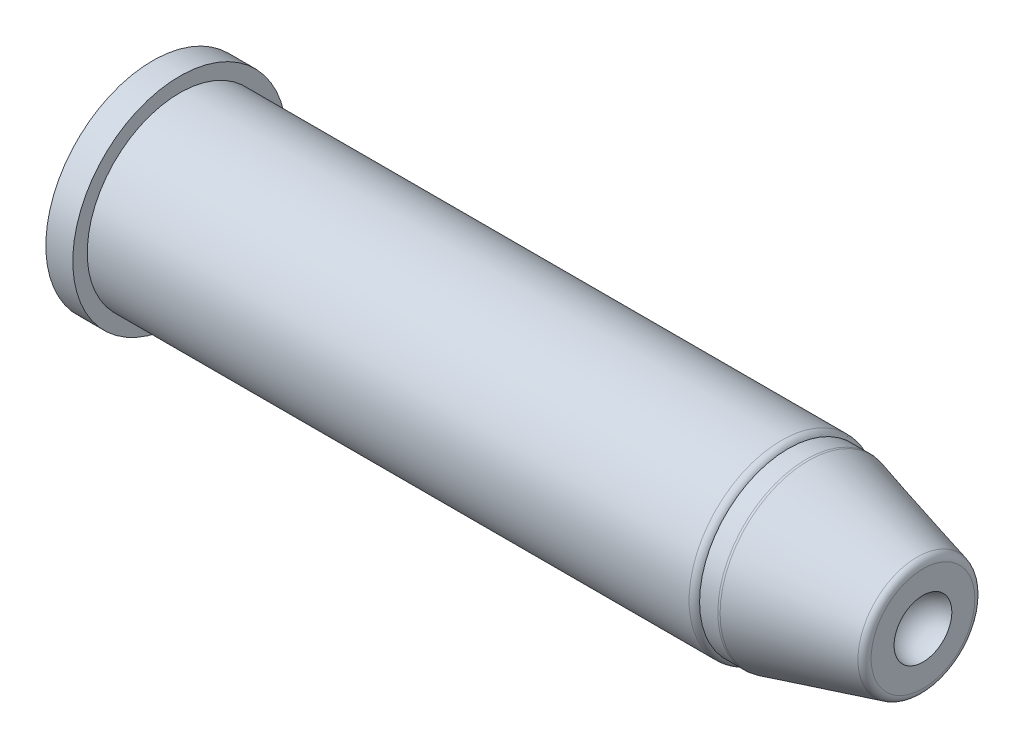
SolidWorks part; units mm, degrees
ref_plane "Plano frontal" through (0, 0, 0) normal (0, 0, 1) x (1, 0, 0)
ref_plane "Plano superior" through (0, 0, 0) normal (0, 1, 0) x (1, 0, 0)
ref_plane "Plano direito" through (0, 0, 0) normal (1, 0, 0) x (0, 0, -1)
sketch "Esboço1" plane through (0, 0, 0) normal (0, 0, 1) x (1, 0, 0)
  line L0 (0, 0) -> (0, 5.55)
  line L1 (0, 5.55) -> (1.4, 5.55)
  line L2 (1.4, 5.55) -> (1.4, 4.8)
  line L3 (1.4, 4.8) -> (33, 4.8)
  line L4 (33, 4.8) -> (33, 4.6)
  line L5 (33, 4.6) -> (34, 4.6)
  line L6 (34, 4.6) -> (40, 3)
  line L7 (40, 3) -> (40, 1.5)
  line L8 (38.5, 0) -> (0, 0)
  arc A0 (40, 1.5) -> (38.5, 0) centre (40, 0) ccw
  point P7 (0.7, 5.55)
  dimension "D10" = 1.5
  dimension "D2" = 5.55
  dimension "D3" = 1.4
  dimension "D4" = 0.2
  dimension "D5" = 4.8
  dimension "D6" = 4.6
  dimension "D7" = 1
  dimension "D8" = 6
  dimension "D9" = 31.6
  dimension "D11" = 1.5
  dimension "D12" = 1.6
  dimension "D13" = 1.5
  dimension "D14" = 1.5
revolve "Revolução1" add sketch "Esboço1" angle 360 about L8
fillet "Filete1" radius 0.4 1 edges at (33, 0, -4.8)
fillet "Filete2" radius 0.4 1 edges at (34, 0, -4.6)
fillet "Filete3" radius 0.4 1 edges at (40, 0, -3)
